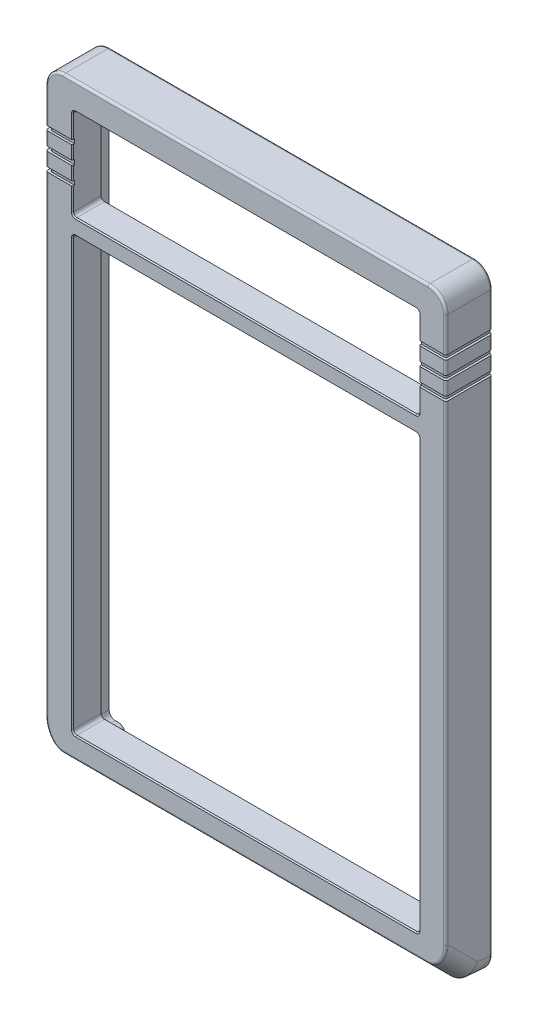
SolidWorks part; units mm, degrees
ref_plane "前视基准面" through (0, 0, 0) normal (0, 0, 1) x (1, 0, 0)
ref_plane "上视基准面" through (0, 0, 0) normal (0, 1, 0) x (1, 0, 0)
ref_plane "右视基准面" through (0, 0, 0) normal (1, 0, 0) x (0, 0, -1)
sketch "草图1" plane through (0, 0, 0) normal (1, 0, 0) x (0, 0, -1)
  line L0 (0, 0) -> (0, 137)
  line L1 (0, 137) -> (-11.4, 137)
  line L2 (-11.4, 137) -> (-11.4, 5.7169)
  line L3 (-11.4, 5.7169) -> (-6.1321, 0.449)
  line L5 (-11.4, 5.7169) -> (6.3075, 5.7169) construction
  line L6 (0, 0) -> (-5.7899, 0) construction
  line L7 (0, 0) -> (-1, 0)
  line L8 (-6.1321, 0.449) -> (-1, 0)
  dimension "D1" = 11.4
  dimension "D2" = 137
  dimension "D3" = 45
  dimension "D4" = 5
  dimension "D5" = 1
  dimension "D6" = 7.45
extrude "凸台-拉伸1" add sketch "草图1" along normal blind 89.5
sketch "草图2" plane through (0, 0, 0) normal (0, 0, -1) x (-1, 0, 0)
  line L0 (0, 0) -> (0, 137) construction
  line L1 (-87.9, 135.4) -> (-1.6, 135.4)
  line L2 (-87.9, 135.4) -> (-87.9, 1.5)
  line L3 (-87.9, 1.5) -> (-1.6, 1.5)
  line L4 (-1.6, 135.4) -> (-1.6, 1.5)
  line L5 (-89.5, 137) -> (0, 137) construction
  line L6 (-89.5, 0) -> (-89.5, 137) construction
  line L7 (-89.5, 0) -> (0, 0) construction
  dimension "D1" = 1.6
  dimension "D2" = 1.6
  dimension "D3" = 1.6
  dimension "D4" = 1.5
extrude "切除-拉伸1" cut sketch "草图2" against normal blind 1 flip side to cut
sketch "草图5" plane through (0, 0, 0) normal (0, 0, -1) x (-1, 0, 0)
  line L0 (-102.6154, 68.5) -> (30.5586, 68.5) construction
  line L1 (-89.5, 0) -> (0, 0) construction
  line L3 (-89.5, 0) -> (-89.5, 137) construction
  line L4 (0, 0) -> (0, 137) construction
  line L5 (0, 137) -> (-89.5, 137) construction
  circle A0 centre (-84.95, 4.55) radius 0.9
  circle A1 centre (-4.55, 4.55) radius 0.9
  circle A2 centre (-4.55, 132.45) radius 0.9
  circle A3 centre (-84.95, 132.45) radius 0.9
  dimension "D1" = 1.8
  dimension "D2" = 4.55
  dimension "D3" = 4.55
  dimension "D4" = 4.55
  dimension "D5" = 4.55
extrude "切除-拉伸3" cut sketch "草图5" against normal blind 6
sketch "草图6" plane through (0, 0, 0) normal (0, 0, -1) x (-1, 0, 0)
  line L0 (-83.2, 2.7) -> (-6.3, 2.7)
  line L1 (-2.8, 70.55) -> (-2.8, 6.2)
  line L2 (-2.8, 70.55) -> (-2.8, 130.7)
  line L3 (-83.2, 134.2) -> (-6.3, 134.2)
  line L4 (-86.7, 130.7) -> (-86.7, 74.35)
  line L5 (-86.7, 74.35) -> (-86.7, 6.2)
  line L6 (-1.6, 1.5) -> (-1.6, 135.4) construction
  line L7 (-87.9, 1.5) -> (-1.6, 1.5) construction
  line L8 (-87.9, 135.4) -> (-87.9, 1.5) construction
  line L9 (-1.6, 135.4) -> (-87.9, 135.4) construction
  line L10 (-83.2, 2.7) -> (-83.2, 6.2)
  line L11 (-83.2, 6.2) -> (-86.7, 6.2)
  line L12 (-6.3, 2.7) -> (-6.3, 6.2)
  line L13 (-6.3, 6.2) -> (-2.8, 6.2)
  line L17 (-6.3, 134.2) -> (-6.3, 130.7)
  line L18 (-6.3, 130.7) -> (-2.8, 130.7)
  line L19 (-86.7, 130.7) -> (-83.2, 130.7)
  line L20 (-83.2, 130.7) -> (-83.2, 134.2)
  dimension "D1" = 1.2
  dimension "D2" = 1.2
  dimension "D3" = 1.2
  dimension "D4" = 1.2
  dimension "D5" = 4.7
extrude "切除-拉伸4" cut sketch "草图6" against normal blind 5
fillet "圆角1" radius 1.4 8 edges at (86.7, 6.2, 2.5) (83.2, 2.7, 2.5) (2.8, 6.2, 2.5) (6.3, 2.7, 2.5) (2.8, 130.7, 2.5) (6.3, 134.2, 2.5) (86.7, 130.7, 2.5) (83.2, 134.2, 2.5)
fillet "圆角2" radius 1.4 4 edges at (6.3, 6.2, 2.5) (83.2, 6.2, 2.5) (6.3, 130.7, 2.5) (83.2, 130.7, 2.5)
sketch "草图3" plane through (0, 0, 0) normal (0, 0, -1) x (-1, 0, 0)
  line L0 (-44.75, 159.1782) -> (-44.75, -24.9782) construction
  line L1 (0, 137) -> (-89.5, 137) construction
  line L2 (-83.5, 106.95) -> (-6, 106.95)
  line L3 (-83.5, 106.95) -> (-83.5, 10.25)
  line L4 (-83.5, 10.25) -> (-6, 10.25)
  line L5 (-6, 106.95) -> (-6, 10.25)
  line L6 (-83.5, 106.95) -> (-6, 10.25) construction
  line L7 (-83.5, 10.25) -> (-6, 106.95) construction
  line L8 (-89.5, 0) -> (0, 0) construction
  line L9 (-83.5, 131) -> (-6, 131)
  line L10 (-83.5, 131) -> (-83.5, 110.5)
  line L11 (-83.5, 110.5) -> (-6, 110.5)
  line L12 (-6, 131) -> (-6, 110.5)
  point P2 (-44.75, 58.6)
  dimension "D1" = 77.5
  dimension "D2" = 10.25
  dimension "D3" = 96.7
  dimension "D4" = 6
  dimension "D5" = 20.5
extrude "切除-拉伸2" cut sketch "草图3" against normal up to surface (11.4 mm away) up to face at (44.75, 71.3585, 11.4)
fillet "圆角9" radius 0.75 8 edges at (83.5, 106.95, 8.2) (6, 106.95, 8.2) (6, 10.25, 8.2) (83.5, 10.25, 8.2) (6, 131, 8.2) (83.5, 131, 8.2) (6, 110.5, 8.2) (83.5, 110.5, 8.2)
fillet "圆角4" radius 4 6 edges at (89.5, 3.083, 8.766) (89.5, 0.2245, 3.566) (0, 3.083, 8.766) (0, 0.2245, 3.566) (0, 137, 6.2) (89.5, 137, 6.2)
fillet "圆角7" radius 2.2 4 edges at (1.6, 1.5, 0.5) (87.9, 1.5, 0.5) (1.6, 135.4, 0.5) (87.9, 135.4, 0.5)
fillet "圆角8" radius 0.5 27 edges at (88.3284, 1.5789, 5.6052) (1.1716, 1.5789, 5.6052) (88.3284, 135.8284, 11.4) (89.5, 72.1869, 11.4) (88.3284, 7.3738, 11.4) (44.75, 5.7169, 11.4) (1.1716, 7.3738, 11.4) (0, 72.1869, 11.4) (1.1716, 135.8284, 11.4) (1.1716, 135.8284, 1) (0, 68.5076, 1) (1.1716, 1.176, 1) (44.75, 0, 1) (88.3284, 1.176, 1) (89.5, 68.5076, 1) (88.3284, 135.8284, 1) (2.2444, 134.7556, 0) (1.6, 68.45, 0) (2.2444, 2.1444, 0) (44.75, 1.5, 0) (87.2556, 2.1444, 0) (87.9, 68.45, 0) (87.2556, 134.7556, 0) (44.75, 0.449, 6.1321) (44.75, 137, 11.4) (44.75, 137, 1) (44.75, 135.4, 0)
chamfer "倒角1" distance 0.25 angle 45 16 edges at (44.75, 10.25, 11.4) (83.5, 58.6, 11.4) (6, 58.6, 11.4) (44.75, 106.95, 11.4) (83.2803, 10.4697, 11.4) (6.2197, 10.4697, 11.4) (83.2803, 106.7303, 11.4) (6.2197, 106.7303, 11.4) (83.2803, 110.7197, 11.4) (83.5, 120.75, 11.4) (83.2803, 130.7803, 11.4) (44.75, 131, 11.4) (6.2197, 130.7803, 11.4) (44.75, 110.5, 11.4) (6.2197, 110.7197, 11.4) (6, 120.75, 11.4)
sketch "草图7" plane through (0, 0, 11.4) normal (0, 0, 1) x (1, 0, 0)
  line L0 (95.3844, 120.75) -> (-7.2026, 120.75)
  line L1 (93.3171, 124.75) -> (-6, 124.75)
  line L2 (93.3171, 116.75) -> (-4.4, 116.75)
  dimension "D1" = 4
extrude "切除-拉伸-薄壁1" cut sketch "草图7" against normal blind 0.5 thin thin type mid plane wall 1
sketch "草图8" plane through (89.5, 0, 0) normal (1, 0, 0) x (0, 0, -1)
  line L0 (-14.7436, 120.75) -> (0.3077, 120.75) construction
  line L2 (-14.4559, 124.75) -> (0, 124.75)
  line L3 (0, 133.2) -> (0, 3.7) construction
  line L4 (-14.4559, 116.75) -> (-0.5, 116.75)
  line L5 (-0.5, 3.7) -> (-0.5, 133.2) construction
  line L6 (-14.4559, 120.75) -> (0.672, 120.75)
  dimension "D1" = 4
extrude "切除-拉伸-薄壁2" cut sketch "草图8" against normal blind 0.5 thin thin type mid plane wall 1
sketch "草图9" plane through (0, 0, 0) normal (-1, 0, 0) x (0, 0, 1)
  line L0 (12.2607, 120.75) -> (-2.117, 120.75) construction
  line L1 (12.385, 124.75) -> (-1.164, 124.75)
  line L2 (12.385, 116.75) -> (-1.164, 116.75)
  line L3 (-1.164, 120.75) -> (12.2607, 120.75)
  dimension "D1" = 4
extrude "切除-拉伸-薄壁3" cut sketch "草图9" against normal blind 0.5 thin thin type mid plane wall 1
fillet "圆角10" radius 0.5 6 edges at (89, 116.75, 10.9) (89, 120.75, 10.9) (89, 124.75, 10.9) (0.5, 116.75, 10.9) (0.5, 120.75, 10.9) (0.5, 124.75, 10.9)
